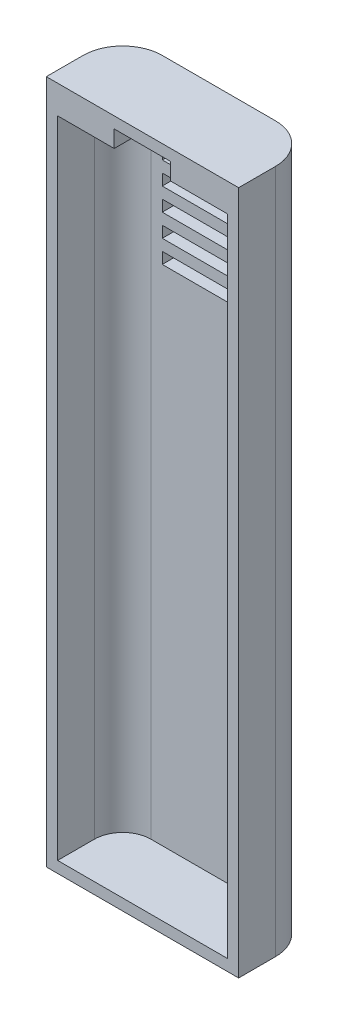
SolidWorks part; units mm, degrees
ref_plane "Plano frontal" through (0, 0, 0) normal (0, 0, 1) x (1, 0, 0)
ref_plane "Plano superior" through (0, 0, 0) normal (0, 1, 0) x (1, 0, 0)
ref_plane "Plano direito" through (0, 0, 0) normal (1, 0, 0) x (0, 0, -1)
sketch "Esboço1" plane through (0, 0, 0) normal (0, 0, 1) x (1, 0, 0)
  line L0 (0, -57) -> (0, 57)
  line L1 (-15, 57) -> (15, 57)
  line L2 (15, 57) -> (15, -57)
  line L3 (15, 0) -> (-15, 0)
  line L4 (-15, 57) -> (-15, -57)
  line L5 (-15, -57) -> (15, -57)
  line L6 (-17, -41) -> (-8, -41)
  line L7 (-17, -52) -> (-8, -52)
  line L8 (-8, 27) -> (-8, 19)
  line L9 (8, -41) -> (17, -41)
  line L10 (8, 27) -> (8, 19)
  line L11 (-8, 57) -> (-8, -57) construction
  line L12 (8, -52) -> (17, -52)
  line L13 (-15, -41) -> (15, -41) construction
  line L14 (-15, 27) -> (15, 27)
  line L15 (-15, -52) -> (15, -52) construction
  line L16 (-15, 19) -> (-8, 19)
  line L17 (8, 19) -> (15, 19)
  line L18 (8, -41) -> (8, -52)
  line L19 (-15, 19) -> (15, 19) construction
  line L20 (-8, -41) -> (-8, -52)
  line L21 (-15, 60) -> (15, 60)
  line L22 (-15, 60) -> (-15, 57)
  line L23 (0, 60) -> (0, 57)
  line L24 (15, 60) -> (15, 57)
  line L25 (5, 60) -> (5, 57)
  line L26 (-5, 60) -> (-5, 57)
  line L27 (-17, 57) -> (-17, -59)
  line L28 (-17, -59) -> (17, -59)
  line L29 (17, 57) -> (17, -59)
  line L30 (17, 62) -> (17, 57)
  line L31 (-17, 62) -> (17, 62)
  line L32 (-17, 62) -> (-17, 57)
  point P8 (0, 0)
  point P16 (8, 57)
  point P17 (8, -57)
sketch "Esboço2" plane through (0, 0, 0) normal (0, 0, 1) x (1, 0, 0)
  line L0 (-8, 27) -> (8, 27)
  line L1 (-17, 62) -> (17, 62)
  line L2 (-17, 62) -> (-17, -59)
  line L3 (-17, -59) -> (17, -59)
  line L4 (17, 62) -> (17, -59)
  line L5 (-15, 27) -> (-8, 27)
  line L6 (-15, 27) -> (-15, 19)
  line L7 (-15, 19) -> (-8, 19)
  line L8 (-8, 27) -> (-8, 19)
  line L9 (8, 19) -> (15, 19)
  line L10 (8, 19) -> (8, 27)
  line L11 (8, 27) -> (15, 27)
  line L12 (15, 19) -> (15, 27)
  line L13 (-8, 30) -> (8, 30)
  line L15 (15, 54) -> (15, 30)
  line L16 (15, 57) -> (15, -57) construction
  line L17 (15, 30) -> (8, 30)
  line L18 (-8, 30) -> (-15, 30)
  line L19 (-15, 57) -> (-15, -57) construction
  line L20 (-15, 30) -> (-15, 54)
  line L21 (-15, 54) -> (15, 54)
extrude "Ressalto-extrusão1" add sketch "Esboço1" along normal blind 6.5 contours L31 L32 L27 L6 L4 L22 L21 L24 L2 L9 L29 L30 | L29 L9 L2 L12 | L29 L12 L2 L5 L4 L7 L27 L28 | L6 L27 L7 L4 | L21 L25 L1 L24 | L26 L21 L22 L1 region at (0, -57.2045, 0) region at (16.0847, 9.5, 0) region at (-16, -46.5, 0) region at (16, -46.5, 0) region at (-10, 58.5, 0) region at (10, 58.5, 0)
sketch "Esboço4" plane through (0, 0, 0) normal (0, 1, 0) x (1, 0, 0)
  line L0 (-17, -6.5) -> (-17, 0)
  line L1 (-17, 0) -> (17, 0)
  line L2 (17, 0) -> (17, -6.5)
  line L3 (17, -6.5) -> (-17, -6.5)
  line L4 (-17, 0) -> (-17, 7)
  line L5 (-17, 7) -> (17, 7)
  line L6 (17, 7) -> (17, 0)
  line L7 (0, 7) -> (0, 0)
  line L8 (0, 7) -> (-10, 7)
  line L9 (-10, 7) -> (-10, 0)
  line L10 (-10, 5) -> (10, 5)
  line L12 (-17, 0) -> (-20.7554, 0)
  line L13 (-17, 0) -> (-17, 11.0707)
  line L14 (17, 11.0707) -> (-20.7554, 11.0707)
  line L15 (-20.7554, 0) -> (-20.7554, 11.0707)
  line L16 (17, 0) -> (20.4417, 0)
  line L17 (17, 0) -> (17, 11.0707)
  line L18 (17, 11.0707) -> (20.4417, 11.0707)
  line L19 (20.4417, 0) -> (20.4417, 11.0707)
  arc A0 (-10, 7) -> (-17, 0) centre (-10, 0) ccw
  arc A1 (-10, 5) -> (-15, 0) centre (-10, 0) ccw
  arc A2 (10, 7) -> (17, 0) centre (10, 0) cw
  arc A3 (10, 5) -> (15, 0) centre (10, 0) cw
  point P24 (0, 5)
  dimension "D1" = 2
extrude "Ressalto-extrusão2" add sketch "Esboço4" along normal blind 62 contours A1 L9 A0 L1 | L9 L10 L7 L5 | L10 A3 L1 A2 L5 L7 region at (-13.8551, 0, -3.8551) region at (-5, 0, -6) region at (16, 0, -0.1838)
extrude "Ressalto-extrusão3" add sketch "Esboço4<3>" against normal blind 59 contours L9 L10 L7 L5 | A1 L9 A0 L1 | L10 A3 L1 A2 L5 L7 region at (-13.8551, 0, -3.8551) region at (-5, 0, -6) region at (16, 0, -0.1838)
sketch "Esboço4<3>" plane through (0, 0, 0) normal (0, 1, 0) x (1, 0, 0) same geometry as "Esboço4"
sketch "Esboço6" plane through (0, -59, 0) normal (0, -1, 0) x (1, 0, 0)
  line L0 (-17, 0) -> (-17, 6.5)
  line L1 (-17, 6.5) -> (17, 6.5)
  line L2 (17, 6.5) -> (17, 0)
  line L4 (10, -7) -> (-10, -7)
  arc A0 (-17, 0) -> (-10, -7) centre (-10, 0) ccw
  arc A1 (10, -7) -> (17, 0) centre (10, 0) ccw
  arc A2 (10, -7) -> (17, 0) centre (10, 0) ccw
  arc M9 (10, -7) -> (17, 0) centre (10, 0) ccw
  line M10 (17, 0) -> (17, 6.5)
  line M11 (17, 6.5) -> (-17, 6.5)
  line M12 (-17, 6.5) -> (-17, 0)
  arc M13 (-17, 0) -> (-10, -7) centre (-10, 0) ccw
  line M14 (-10, -7) -> (10, -7)
  line M15 (-15, 0) -> (15, 0)
  arc M16 (15, 0) -> (10, -5) centre (10, 0) cw
  line M17 (10, -5) -> (-10, -5)
  arc M18 (-10, -5) -> (-15, 0) centre (-10, 0) cw
extrude "Ressalto-extrusão4" add sketch "Esboço6" against normal blind 2 contours M14 M9 M10 M11 M12 M13 M18 M15 M16 M17 | M15 M18 M17 M16 region at (0, -59, 1.1146) region at (0, -59, -2.3934)
sketch "Esboço7" plane through (0, 62, 0) normal (0, 1, 0) x (1, 0, 0)
  line L0 (17, 0) -> (17, -6.5)
  line L1 (17, -6.5) -> (-17, -6.5)
  line L2 (-17, -6.5) -> (-17, 0)
  line L3 (-17, 0) -> (-10, 0)
  line L4 (-10, 0) -> (10, 0)
  line L5 (10, 7) -> (-10, 7)
  arc A0 (17, 0) -> (10, 7) centre (10, 0) ccw
  arc A1 (-10, 7) -> (-17, 0) centre (-10, 0) ccw
  line M7 (17, -6.5) -> (17, 0)
  arc M8 (17, 0) -> (10, 7) centre (10, 0) ccw
  line M9 (10, 7) -> (-10, 7)
  arc M10 (-10, 7) -> (-17, 0) centre (-10, 0) ccw
  line M11 (-17, 0) -> (-17, -6.5)
  line M12 (-17, -6.5) -> (17, -6.5)
  line M13 (15, 0) -> (-15, 0)
  arc M14 (-15, 0) -> (-10, 5) centre (-10, 0) cw
  line M15 (-10, 5) -> (10, 5)
  arc M16 (10, 5) -> (15, 0) centre (10, 0) cw
extrude "Ressalto-extrusão5" add sketch "Esboço7" against normal blind 2 contours M12 M7 M8 M9 M10 M14 M15 M16 M13 M11 | M13 M16 M15 M14 region at (0, 62, -2.3934) region at (0, 62, 1.1146)
sketch "Esboço8" plane through (0, 0, -7) normal (0, 0, -1) x (-1, 0, 0)
  line L0 (15, 54) -> (-15, 54) construction
  line L1 (-8, 30) -> (8, 30)
  line L2 (-8, 30) -> (-8, 54)
  line L3 (-8, 54) -> (8, 54)
  line L4 (8, 30) -> (8, 54)
  line L5 (-8, 52) -> (8, 52)
  line L6 (-8, 48) -> (8, 48)
  line L7 (-8, 50) -> (8, 50)
  line L8 (-8, 46) -> (8, 46)
  line L9 (-8, 44) -> (8, 44)
  line L10 (-8, 42) -> (8, 42)
  line L11 (-8, 40) -> (8, 40)
  line L12 (-8, 38) -> (8, 38)
  line L13 (-8, 36) -> (8, 36)
  line L14 (-8, 34) -> (8, 34)
  line L15 (-8, 32) -> (8, 32)
extrude "Corte-extrusão1" cut sketch "Esboço8" against normal mid plane 20 contours L2 L5 L4 L3 | L7 L2 L6 L4 | L2 L9 L4 L8 | L2 L11 L4 L10 | L2 L13 L4 L12 | L2 L15 L4 L14 region at (0, 33, -7) region at (0, 37, -7) region at (0, 41, -7) region at (0, 45, -7) region at (0, 49, -7) region at (0, 53, -7)
